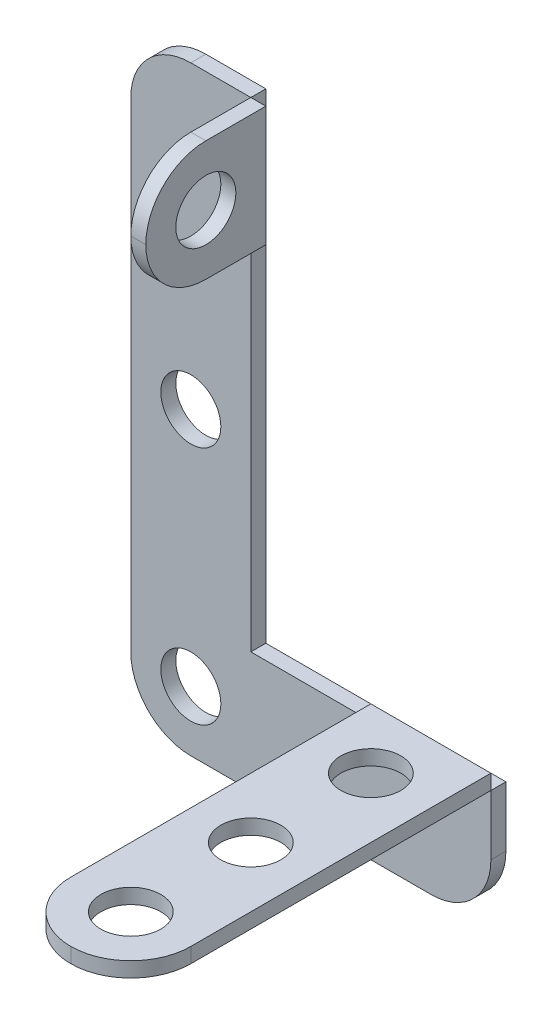
SolidWorks part; units mm, degrees
ref_plane "Front Plane" through (0, 0, 0) normal (0, 0, 1) x (1, 0, 0)
ref_plane "Top Plane" through (0, 0, 0) normal (0, 1, 0) x (1, 0, 0)
ref_plane "Right Plane" through (0, 0, 0) normal (1, 0, 0) x (0, 0, -1)
sketch "Sketch1" plane through (0, 0, 0) normal (0, 0, 1) x (1, 0, 0)
  line L0 (12.7, 0) -> (38.1, 0)
  line L1 (12.7, 0) -> (0, 0)
  line L3 (12.7, 63.5) -> (0, 63.5)
  line L4 (0, 0) -> (0, 63.5)
  line L5 (38.1, 0) -> (38.1, 12.7)
  line L6 (38.1, 12.7) -> (12.7, 12.7)
  line L7 (12.7, 63.5) -> (12.7, 12.7)
  line L8 (6.35, 63.5) -> (6.35, 0) construction
  circle A0 centre (6.35, 31.75) radius 3.175
  circle A1 centre (6.35, 6.35) radius 3.175
  dimension "D1" = 6.35
  dimension "D2" = 31.75
  dimension "D3" = 12.7
  dimension "D4" = 25.4
  dimension "D5" = 6.35
  dimension "D6" = 25.4
extrude "Boss-Extrude1" add sketch "Sketch1" along normal blind 1.5875
sketch "Sketch2" plane through (12.7, 0, 0) normal (1, 0, 0) x (0, 0, -1)
  line L0 (-14.2875, 50.8) -> (-1.5875, 63.5) construction
  line L1 (-1.5875, 63.5) -> (-14.2875, 63.5)
  line L2 (-1.5875, 63.5) -> (-1.5875, 50.8)
  line L3 (-1.5875, 50.8) -> (-14.2875, 50.8)
  line L4 (-14.2875, 63.5) -> (-14.2875, 50.8)
  line L5 (-14.2875, 63.5) -> (-1.5875, 50.8) construction
  circle A0 centre (-7.9375, 57.15) radius 3.175
  point P5 (-7.9375, 57.15)
  dimension "D3" = 6.35
  dimension "D1" = 12.7
  dimension "D2" = 6.35
extrude "Boss-Extrude2" add sketch "Sketch2" along normal blind 1.5875 separate body
sketch "Sketch3" plane through (0, 12.7, 0) normal (0, 1, 0) x (1, 0, 0)
  line L0 (31.75, -1.5875) -> (31.75, -39.6875) construction
  line L1 (38.1, -1.5875) -> (25.4, -1.5875)
  line L2 (38.1, -1.5875) -> (38.1, -39.6875)
  line L3 (38.1, -39.6875) -> (25.4, -39.6875)
  line L4 (25.4, -1.5875) -> (25.4, -39.6875)
  circle A0 centre (31.75, -7.9375) radius 3.175
  circle A1 centre (31.75, -20.6375) radius 3.175
  circle A2 centre (31.75, -33.3375) radius 3.175
  dimension "D2" = 6.35
  dimension "D1" = 12.7
  dimension "D3" = 6.35
  dimension "D4" = 12.7
  dimension "D5" = 6.35
  dimension "D6" = 12.7
extrude "Boss-Extrude3" add sketch "Sketch3" along normal blind 1.5875 separate body
fillet "Fillet1" radius 6.35 2 edges at (25.4, 13.4937, 39.6875) (38.1, 13.4937, 39.6875)
fillet "Fillet2" radius 6.35 2 edges at (13.4938, 50.8, 14.2875) (13.4937, 63.5, 14.2875)
fillet "Fillet3" radius 6.35 3 edges at (0, 63.5, 0.7937) (0, 0, 0.7937) (38.1, 0, 0.7937)
